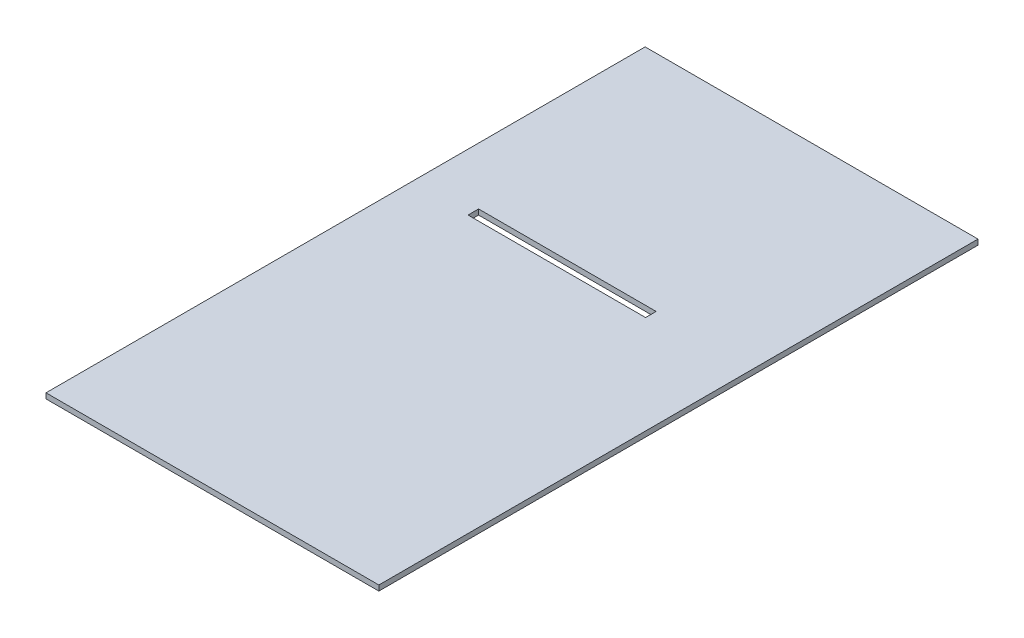
SolidWorks part; units mm, degrees
ref_plane "Front Plane" through (0, 0, 0) normal (0, 0, 1) x (1, 0, 0)
ref_plane "Top Plane" through (0, 0, 0) normal (0, 1, 0) x (1, 0, 0)
ref_plane "Right Plane" through (0, 0, 0) normal (1, 0, 0) x (0, 0, -1)
sketch "Sketch1" plane through (0, 0, 0) normal (0, 1, 0) x (1, 0, 0)
  line L1 (50, -90) -> (-50, -90)
  line L2 (50, -90) -> (50, 90)
  line L3 (50, 90) -> (-50, 90)
  line L4 (-50, -90) -> (-50, 90)
  line L5 (50, -90) -> (-50, 90) construction
  line L6 (50, 90) -> (-50, -90) construction
  point P0 (0, 0)
  dimension "D1" = 100
  dimension "D2" = 180
extrude "Boss-Extrude1" add sketch "Sketch1" along normal blind 1.6
sketch "Sketch2" plane through (0, 1.6, 0) normal (0, 1, 0) x (1, 0, 0)
  line L0 (50, 90) -> (-50, 90) construction
  line L1 (-31.585, 56.599) -> (-10.757, 56.599)
  line L2 (-31.585, 56.599) -> (-31.585, 45.55)
  line L3 (-31.585, 45.55) -> (-10.757, 45.55)
  line L4 (-10.757, 56.599) -> (-10.757, 45.55)
  line L6 (-50, 90) -> (-50, -90) construction
  dimension "D1" = 44.45
  dimension "D2" = 18.415
  dimension "D3" = 20.828
  dimension "D4" = 33.401
extrude "Boss-Extrude2" add sketch "Sketch2" against normal blind 2.159 from surface starting at face at (0, 0, 0)
sketch "Sketch3" plane through (0, 1.6, 0) normal (0, 1, 0) x (1, 0, 0)
  line L0 (-31.585, 45.55) -> (-10.757, 45.55) construction
  line L1 (-31.585, 45.55) -> (-10.757, 45.55)
  line L3 (-32.855, 22.817) -> (-32.855, 19.642)
  line L4 (-32.855, 19.642) -> (20.485, 19.642)
  line L5 (20.485, 19.642) -> (20.485, 22.817)
  line L7 (20.485, 22.817) -> (-32.855, 22.817)
  line L8 (50, 90) -> (-50, 90) construction
  dimension "D1" = 1.27
  dimension "D2" = 3.175
  dimension "D3" = 53.34
  dimension "D4" = 67.183
extrude "Cut-Extrude2" cut sketch "Sketch3" against normal through all contours L5 L7 L3 L4 region at (-6.185, 1.6, -21.2295)
sketch "Sketch4" plane through (0, -2.159, 0) normal (0, -1, 0) x (1, 0, 0)
  line L0 (-31.585, -45.55) -> (-10.757, -45.55) construction
  line L1 (-30.315, -45.55) -> (-12.0156, -45.55)
  line L2 (-30.315, -45.55) -> (-30.315, -55.329)
  line L3 (-30.315, -55.329) -> (-12.0156, -55.329)
  line L4 (-12.0156, -45.55) -> (-12.0156, -55.329)
  line L5 (-31.585, -56.599) -> (-31.585, -45.55) construction
  line L6 (-10.757, -56.599) -> (-31.585, -56.599) construction
  line L7 (-10.757, -45.55) -> (-10.757, -56.599) construction
  dimension "D1" = 1.27
  dimension "D2" = 1.27
  dimension "D3" = 1.2586
extrude "Cut-Extrude3" cut sketch "Sketch4" against normal up to surface (2.159 mm away) up to face at (-6.185, 0, -21.2295)
sketch "Sketch5" plane through (0, 0, 0) normal (0, -1, 0) x (1, 0, 0)
  line L1 (7.5, -34.88) -> (11.5, -34.88)
  line L2 (7.5, -34.88) -> (7.5, -50.08)
  line L3 (7.5, -50.08) -> (11.5, -50.08)
  line L4 (11.5, -34.88) -> (11.5, -50.08)
  line L5 (7.5, -56.38) -> (11.5, -56.38)
  line L6 (7.5, -56.38) -> (7.5, -71.58)
  line L7 (7.5, -71.58) -> (11.5, -71.58)
  line L8 (11.5, -56.38) -> (11.5, -71.58)
  line L9 (43.5, -34.88) -> (47.5, -34.88)
  line L10 (43.5, -34.88) -> (43.5, -50.08)
  line L11 (43.5, -50.08) -> (47.5, -50.08)
  line L12 (47.5, -34.88) -> (47.5, -50.08)
  line L13 (43.5, -60.38) -> (47.5, -60.38)
  line L14 (43.5, -60.38) -> (43.5, -75.58)
  line L15 (43.5, -75.58) -> (47.5, -75.58)
  line L16 (47.5, -60.38) -> (47.5, -75.58)
  line L17 (50, -90) -> (-50, -90) construction
  line L18 (50, 90) -> (50, -90) construction
  point P16 (7.5, -63.98)
  point P17 (7.5, -42.48)
  point P18 (47.5, -67.98)
  point P19 (47.5, -42.48)
  point P22 (45.5, -75.58)
  point P25 (45.5, -34.88)
  point P26 (9.5, -34.88)
  dimension "D1" = 15.2
  dimension "D2" = 4
  dimension "D3" = 21.5
  dimension "D4" = 25.5
  dimension "D5" = 14.42
  dimension "D6" = 4.5
  dimension "D7" = 36
extrude "Boss-Extrude3" add sketch "Sketch5" along normal blind 2.5
sketch "Sketch6" plane through (0, -2.5, 0) normal (0, -1, 0) x (1, 0, 0)
  line L0 (7.5, -56.38) -> (7.5, -71.58) construction
  line L1 (8.0395, -57.503) -> (10.9605, -57.503)
  line L2 (8.0395, -57.503) -> (8.0395, -70.457)
  line L3 (8.0395, -70.457) -> (10.9605, -70.457)
  line L4 (10.9605, -57.503) -> (10.9605, -70.457)
  line L5 (8.0395, -36.003) -> (10.9605, -36.003)
  line L6 (8.0395, -36.003) -> (8.0395, -48.957)
  line L7 (8.0395, -48.957) -> (10.9605, -48.957)
  line L8 (10.9605, -36.003) -> (10.9605, -48.957)
  line L9 (44.0395, -36.003) -> (46.9605, -36.003)
  line L10 (44.0395, -36.003) -> (44.0395, -48.957)
  line L11 (44.0395, -48.957) -> (46.9605, -48.957)
  line L12 (46.9605, -36.003) -> (46.9605, -48.957)
  line L13 (44.0395, -61.503) -> (46.9605, -61.503)
  line L14 (44.0395, -61.503) -> (44.0395, -74.457)
  line L15 (44.0395, -74.457) -> (46.9605, -74.457)
  line L16 (46.9605, -61.503) -> (46.9605, -74.457)
  line L17 (11.5, -56.38) -> (7.5, -56.38) construction
  line L18 (11.5, -56.38) -> (7.5, -56.38)
  line L19 (7.5, -56.38) -> (7.5, -71.58)
  line L20 (7.5, -34.88) -> (7.5, -50.08) construction
  line L21 (7.5, -34.88) -> (7.5, -50.08)
  line L22 (43.5, -60.38) -> (43.5, -75.58) construction
  line L23 (43.5, -60.38) -> (43.5, -75.58)
  line L24 (47.5, -34.88) -> (43.5, -34.88) construction
  line L25 (47.5, -34.88) -> (43.5, -34.88)
  point P16 (9.5, -56.38)
  point P17 (9.5, -57.503)
  point P18 (7.5787, -57.4093)
  point P21 (7.5, -63.98)
  point P23 (8.0395, -63.98)
  point P30 (8.0395, -42.48)
  point P31 (7.5, -42.48)
  point P32 (45.5, -36.003)
  point P33 (45.5, -34.88)
  point P34 (44.0395, -67.98)
  point P35 (43.5, -67.98)
  dimension "D1" = 2.921
  dimension "D2" = 12.954
extrude "Cut-Extrude4" cut sketch "Sketch6" against normal blind 2.032 contours L4 L1 L2 L3 | L8 L5 L6 L7 | L12 L9 L10 L11 | L16 L13 L14 L15 region at (9.5, -2.5, -63.98) region at (9.5, -2.5, -42.48) region at (45.5, -2.5, -42.48) region at (45.5, -2.5, -67.98)
